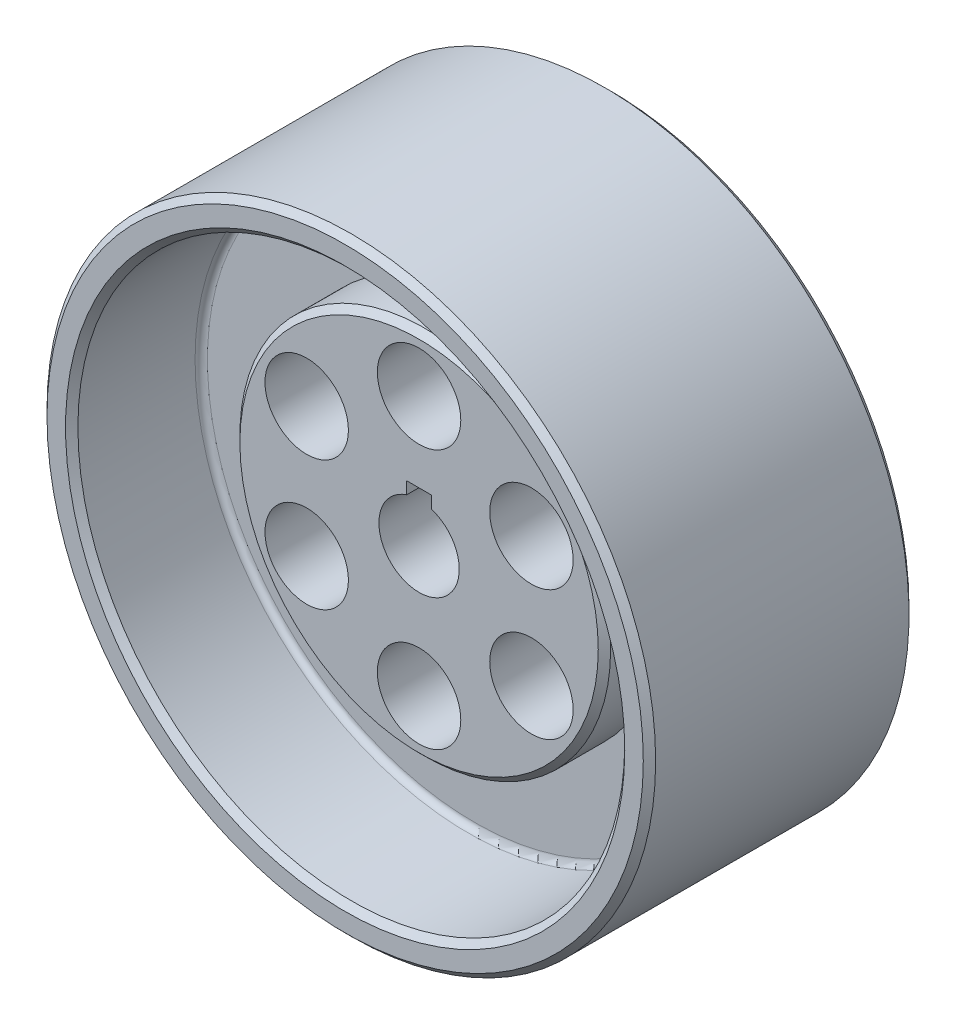
SolidWorks part; units mm, degrees
ref_plane "前视基准面" through (0, 0, 0) normal (0, 0, 1) x (1, 0, 0)
ref_plane "上视基准面" through (0, 0, 0) normal (0, 1, 0) x (1, 0, 0)
ref_plane "右视基准面" through (0, 0, 0) normal (1, 0, 0) x (0, 0, -1)
sketch "草图2" plane through (0, 0, 0) normal (1, 0, 0) x (0, 0, -1)
  line L0 (0, 0) -> (0, 98.5)
  line L1 (0, 55) -> (0, -55) construction
  line L2 (0, 98.5) -> (86, 98.5)
  line L3 (86, 98.5) -> (86, 25)
  line L4 (86, 25) -> (104, 25)
  line L5 (104, 25) -> (104, 0)
  line L6 (55, 0) -> (-55, 0) construction
  line L7 (104, 0) -> (0, 0) construction
  line L8 (0, 0) -> (104, 0)
  dimension "D1" = 104
  dimension "D2" = 50
  dimension "D3" = 197
  dimension "D4" = 86
revolve "旋转1" add sketch "草图2" angle 360 about L7
sketch "草图3" plane through (0, 0, 0) normal (1, 0, 0) x (0, 0, -1)
  line L0 (0, 0) -> (0, 88.5)
  line L1 (0, 108.35) -> (0, -108.35) construction
  line L2 (0, 88.5) -> (41.9272, 88.5)
  line L3 (41.9272, 88.5) -> (41.9272, 60)
  line L4 (41.9272, 60) -> (23.9272, 60)
  line L5 (23.9272, 60) -> (23.9272, 0)
  line L6 (57.2, 0) -> (-57.2, 0) construction
  line L7 (23.9272, 0) -> (0, 0) construction
  line L8 (86, 88.5) -> (49, 88.5)
  line L9 (86, -98.5) -> (86, 98.5) construction
  line L10 (49, 88.5) -> (49, 25)
  line L11 (49, 25) -> (86, 25)
  line L12 (86, -25) -> (86, 25) construction
  line L13 (86, 25) -> (86, 88.5)
  line L14 (23.9272, 0) -> (0, 0)
  line L15 (23.9272, 0) -> (156.7137, 0) construction
  dimension "D1" = 177
  dimension "D2" = 50
  dimension "D3" = 120
  dimension "D4" = 18
  dimension "D5" = 41.9272
  dimension "D6" = 37
revolve "切除-旋转1" cut sketch "草图3" angle 360 about L15
fillet "圆角1" radius 2 2 edges at (88.5, 0, -41.9272) (88.5, 0, -49)
chamfer "倒角1" distance 2 angle 45 5 edges at (60, 0, -23.9272) (-98.5, 0, 0) (88.5, 0, 0) (88.5, 0, -86) (-98.5, 0, -86)
sketch "草图4" plane through (0, 0, -23.9272) normal (0, 0, 1) x (1, 0, 0)
  line L0 (0, 13) -> (4, 9.7) construction
  line L1 (-4, 9.7) -> (4, 9.7) construction
  line L2 (-4, 12.3693) -> (-4, 16.3)
  line L3 (-4, 16.3) -> (4, 16.3)
  line L4 (4, 12.3693) -> (4, 16.3)
  line L5 (0, 13) -> (4, 16.3) construction
  line L6 (-4, 16.3) -> (0, 13) construction
  line L7 (4, 9.7) -> (4, 12.3693) construction
  line L8 (-4, 9.7) -> (0, 13) construction
  line L9 (-4, 9.7) -> (-4, 12.3693) construction
  arc A0 (-4, 12.3693) -> (4, 12.3693) centre (0, 0) ccw
  arc A1 (0, 13) -> (-4, 12.3693) centre (0, 0) ccw construction
  arc A2 (4, 12.3693) -> (0, 13) centre (0, 0) ccw construction
  point P3 (0, 13)
  dimension "D1" = 26
  dimension "D2" = 29.3
  dimension "D3" = 8
extrude "切除-拉伸1" cut sketch "草图4" against normal through all
hole_wizard "M8 螺纹孔1" positions "3D草图1" profile "草图5" tap size "M8" standard "GB" end condition up to next
sketch3d "3D草图1"
  point P0 (0, -25, -94)
  point P1 (0, 0, 0)
  dimension "D1" = 10
sketch "草图5" plane through (0, -25, -94) normal (1, 0, 0) x (0, 0, -1)
  line L0 (0, 0) -> (0, 12)
  line L1 (0, 12) -> (3.4, 12)
  line L2 (3.4, 12) -> (3.4, 0.625)
  line L3 (3.4, 0.625) -> (4.025, 0)
  line L5 (4.025, 0) -> (0, 0)
  line L6 (-3.4, 0.625) -> (-4.025, 0) construction
  line L11 (0, -6.35) -> (0, 107.95) construction
  dimension "通孔螺纹孔钻头直径" = 6.8
  dimension "通孔螺纹孔钻头深度" = 12
  dimension "近端锥形沉头孔直径" = 8.05
  dimension "近端锥形沉头孔角度" = 90
cosmetic thread "孔螺纹线1" parameters "D2"=8
sketch "草图6" plane through (0, 0, -104) normal (0, 0, -1) x (-1, 0, 0)
  circle A4 centre (0, 0) radius 23
  circle A5 centre (0, 0) radius 23
  dimension "D1" = 2
extrude "切除-拉伸2" cut sketch "草图6" against normal blind 2 from offset 9 flip side to cut offset against normal yes
sketch "草图7" plane through (0, 0, -49) normal (0, 0, -1) x (-1, 0, 0)
  circle A0 centre (0, 0) radius 42 construction
  point P3 (0, 42)
  point P7 (36.3731, 21)
  point P8 (36.3731, -21)
  point P9 (0, -42)
  point P10 (-36.3731, -21)
  point P11 (-36.3731, 21)
  dimension "D1" = 84
  dimension "D2" = 6
hole_wizard "孔1" positions "草图7" profile "草图8" legacy end condition up to next
sketch "草图8" plane through (36.3731, 21, -49) normal (1, 0, 0) x (0, 1, 0)
  line L0 (0, 0) -> (0, 33.1844)
  line L1 (0, 33.1844) -> (13.5, 25.0728)
  line L2 (13.5, 25.0728) -> (13.5, 0)
  line L4 (13.5, 0) -> (0, 0)
  line L6 (0, 33.1844) -> (-13.5, 25.0728) construction
  line L7 (0, -4.2442) -> (0, 117.3081) construction
  dimension "直径" = 27
  dimension "深度" = 25.0728
  dimension "导头角度" = 118
sketch "草图9" plane through (0, 0, -49) normal (0, 0, -1) x (-1, 0, 0)
  circle A0 centre (0, 0) radius 57
  circle A2 centre (0, 0) radius 25
  circle A3 centre (0, 0) radius 25
  dimension "D1" = 114
  dimension "D2" = 0
extrude "切除-拉伸3" cut sketch "草图9" against normal blind 3
fillet "圆角2" radius 2 1 edges at (-25, 0, -46)
